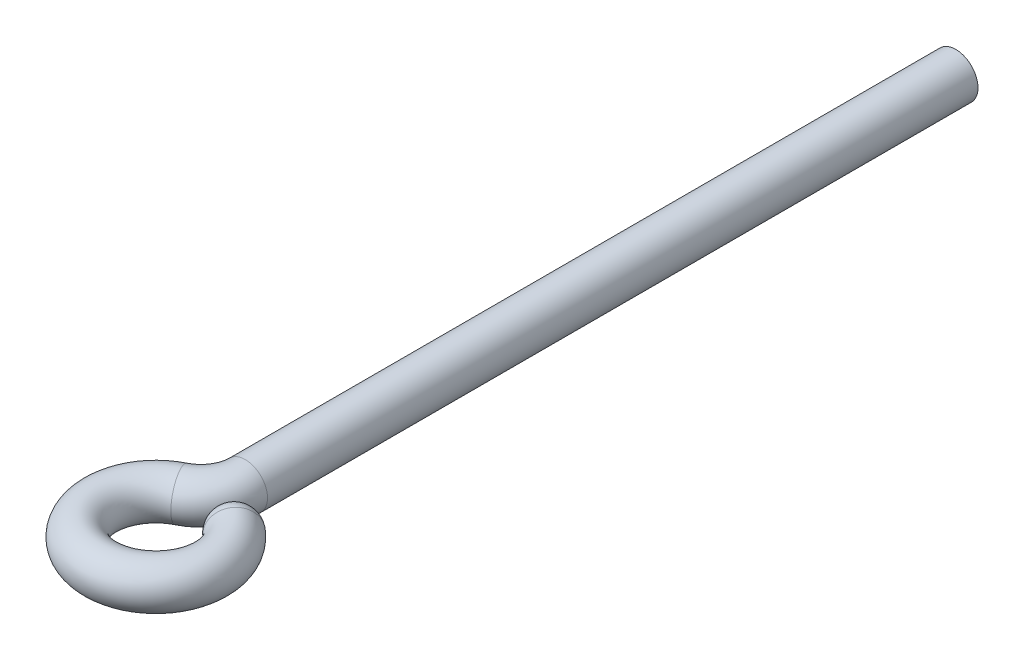
SolidWorks part; units mm, degrees
ref_plane "Front Plane" through (0, 0, 0) normal (0, 0, 1) x (1, 0, 0)
ref_plane "Top Plane" through (0, 0, 0) normal (0, 1, 0) x (1, 0, 0)
ref_plane "Right Plane" through (0, 0, 0) normal (1, 0, 0) x (0, 0, -1)
sketch "Sketch1" plane through (0, 0, 0) normal (0, 0, 1) x (1, 0, 0)
  circle A0 centre (0, 0) radius 1
  dimension "D1" = 2
extrude "Boss-Extrude1" add sketch "Sketch1" against normal blind 30
sketch "Sketch3" plane through (0, 0, 0) normal (0, 1, 0) x (1, 0, 0)
  line L0 (0, 0) -> (0, -2)
  line L1 (0, -6.0311) -> (0, -2.7599) construction
  line L2 (0, -6.0311) -> (1.607, -4.116) construction
  arc A0 (0, -2) -> (-1.1111, -3.7916) centre (-2, -2) cw
  arc A1 (-1.1111, -3.7916) -> (1.607, -4.116) centre (0, -6.0311) ccw
  dimension "D1" = 2
  dimension "D3" = 2.5
  dimension "D2" = 2
  dimension "D4" = 40
sweep "Sweep1" add profiles "Sketch1<2>" path "Sketch3"
sketch "Sketch1<2>" plane through (0, 0, 0) normal (0, 0, 1) x (1, 0, 0) same geometry as "Sketch1"
dome "Dome2" faces to dome 1 distance 1 reverse direction no elliptical dome no face at (0.9642, 0, 4.8821) parameters "D1"=1
